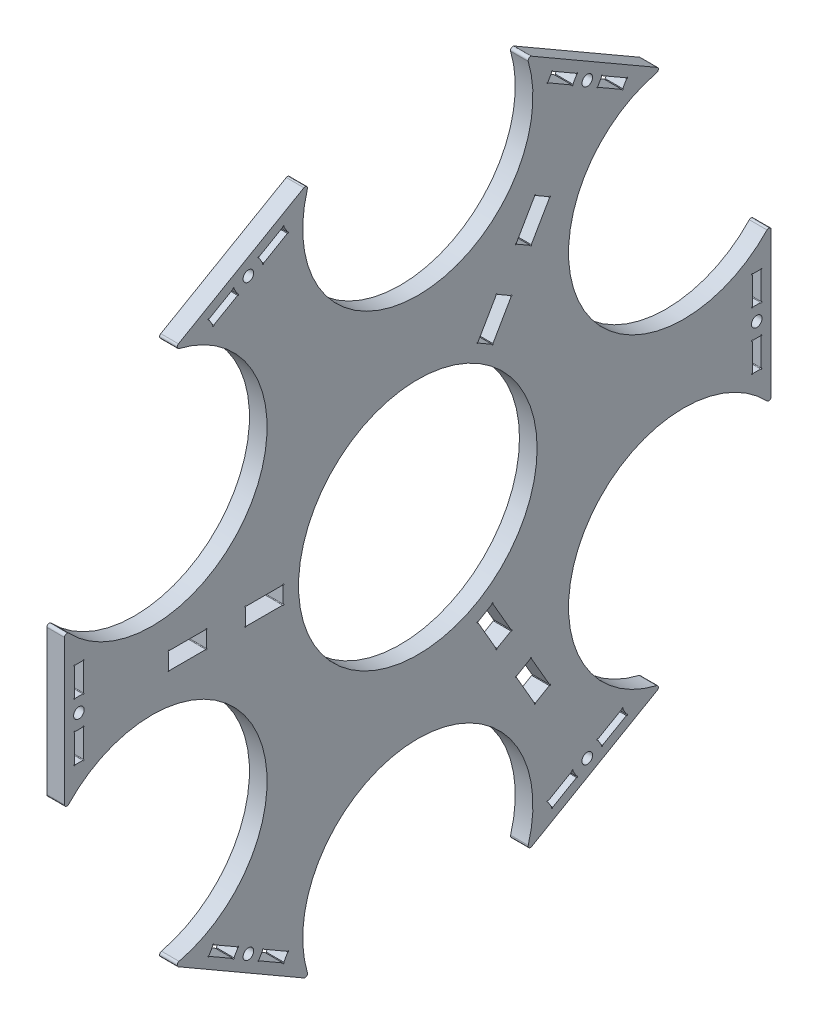
SolidWorks part; units mm, degrees
ref_plane "Front Plane" through (0, 0, 0) normal (0, 0, 1) x (1, 0, 0)
ref_plane "Top Plane" through (0, 0, 0) normal (0, 1, 0) x (1, 0, 0)
ref_plane "Right Plane" through (0, 0, 0) normal (1, 0, 0) x (0, 0, -1)
sketch "Sketch2" plane through (0, 0, 0) normal (1, 0, 0) x (0, 0, -1)
  line L0 (35.921, 114.3) -> (-35.921, 114.3) construction
  line L1 (81.0262, 88.2585) -> (35.921, 114.3)
  line L2 (116.9472, -26.0415) -> (116.9472, 26.0415)
  line L3 (35.921, -114.3) -> (81.0262, -88.2585)
  line L4 (-81.0262, -88.2585) -> (-35.921, -114.3)
  line L5 (-116.9472, 26.0415) -> (-116.9472, -26.0415)
  line L6 (-35.921, 114.3) -> (-81.0262, 88.2585)
  circle A0 centre (0, 0) radius 101.6 construction
  arc A1 (-35.921, 114.3) -> (35.921, 114.3) centre (0, 101.6) ccw
  arc A2 (81.0262, 88.2585) -> (116.9472, 26.0415) centre (87.9882, 50.8) ccw
  arc A3 (116.9472, -26.0415) -> (81.0262, -88.2585) centre (87.9882, -50.8) ccw
  arc A4 (35.921, -114.3) -> (-35.921, -114.3) centre (0, -101.6) ccw
  arc A5 (-81.0262, -88.2585) -> (-116.9472, -26.0415) centre (-87.9882, -50.8) ccw
  arc A6 (-116.9472, 26.0415) -> (-81.0262, 88.2585) centre (-87.9882, 50.8) ccw
  circle A7 centre (0, 0) radius 39.4875
  point P23 (0, 0)
  point P34 (0, 0)
  dimension "D1" = 203.2
  dimension "D2" = 114.3
  dimension "D3" = 76.2
  dimension "D6" = 78.9749
  dimension "D4" = 6
  dimension "D5" = 6
extrude "Boss-Extrude1" add sketch "Sketch2" along normal blind 5.842 contours A6 L5 A5 L4 A4 L3 A3 L2 A2 L1 A1 L6 region at (0, 30.1147, -52.1602)
fillet "Fillet1" radius 0.7937 12 edges at (2.921, -114.3, 35.921) (2.921, -114.3, -35.921) (2.921, -88.2585, -81.0262) (2.921, -26.0415, -116.9472) (2.921, 88.2585, -81.0262) (2.921, 26.0415, -116.9472) (2.921, -88.2585, 81.0262) (2.921, -26.0415, 116.9472) (2.921, 26.0415, 116.9472) (2.921, 88.2585, 81.0262) (2.921, 114.3, -35.921) (2.921, 114.3, 35.921)
sketch "Sketch3" plane through (5.842, 0, 0) normal (1, 0, 0) x (0, 0, -1)
  line L0 (0, 0) -> (0, 50.8) construction
  line L2 (6.1516, 53.721) -> (-6.1516, 53.721)
  line L3 (6.35, 53.5226) -> (6.35, 48.0774)
  line L4 (6.1516, 47.879) -> (-6.1516, 47.879)
  line L5 (-6.35, 53.5226) -> (-6.35, 48.0774)
  line L6 (6.35, 53.721) -> (-6.35, 47.879) construction
  line L7 (6.35, 47.879) -> (-6.35, 53.721) construction
  arc A0 (-6.1516, 53.721) -> (-6.35, 53.5226) centre (-6.35, 53.721) ccw
  arc A1 (-6.35, 48.0774) -> (-6.1516, 47.879) centre (-6.35, 47.879) ccw
  arc A2 (6.1516, 47.879) -> (6.35, 48.0774) centre (6.35, 47.879) ccw
  arc A3 (6.35, 53.5226) -> (6.1516, 53.721) centre (6.35, 53.721) ccw
  dimension "D4" = 0.3969
  dimension "D5" = 0.3969
  dimension "D6" = 0.3969
  dimension "D7" = 0.3969
  dimension "D1" = 50.8
  dimension "D2" = 12.7
  dimension "D3" = 5.842
extrude "Cut-Extrude2" [suppressed] cut sketch "Sketch3" against normal through all
pattern_circular "CirPattern1" [suppressed] count 3 every 120 of bodies 112
sketch "Sketch4" plane through (5.842, 0, 0) normal (1, 0, 0) x (0, 0, -1)
  line L0 (0, 0) -> (25.4, 43.9941) construction
  line L1 (26.0386, 50.8422) -> (19.7886, 40.0169)
  line L2 (26.0386, 50.8422) -> (31.0114, 47.9712)
  line L3 (19.7886, 40.0169) -> (24.7614, 37.1459)
  line L4 (31.0114, 47.9712) -> (24.7614, 37.1459)
  line L5 (26.0386, 50.8422) -> (24.7614, 37.1459) construction
  line L6 (19.7886, 40.0169) -> (31.0114, 47.9712) construction
  line L7 (0, 0) -> (0, 63.5) construction
  line L8 (31.0114, -47.9712) -> (24.7614, -37.1459)
  line L9 (31.0114, -47.9712) -> (26.0386, -50.8422)
  line L10 (24.7614, -37.1459) -> (19.7886, -40.0169)
  line L11 (26.0386, -50.8422) -> (19.7886, -40.0169)
  line L12 (31.0114, -47.9712) -> (19.7886, -40.0169) construction
  line L13 (24.7614, -37.1459) -> (26.0386, -50.8422) construction
  line L14 (-57.05, -2.871) -> (-44.55, -2.871)
  line L15 (-57.05, -2.871) -> (-57.05, 2.871)
  line L16 (-44.55, -2.871) -> (-44.55, 2.871)
  line L17 (-57.05, 2.871) -> (-44.55, 2.871)
  line L18 (-57.05, -2.871) -> (-44.55, 2.871) construction
  line L19 (-44.55, -2.871) -> (-57.05, 2.871) construction
  arc A0 (-36.5501, 112.3566) -> (36.5501, 112.3566) centre (0, 101.6) ccw construction
  point P21 (0, 0)
  dimension "D1" = 50.8
  dimension "D2" = 12.5
  dimension "D3" = 5.742
  dimension "D4" = 30
extrude "Cut-Extrude3" cut sketch "Sketch4" against normal through all
sketch "Sketch5" plane through (5.842, 0, 0) normal (1, 0, 0) x (0, 0, -1)
  line L0 (22.9136, 45.4296) -> (27.8864, 42.5586) construction
  line L3 (26.0386, 50.8422) -> (19.7886, 40.0169) construction
  line L4 (24.7614, 37.1459) -> (31.0114, 47.9712) construction
  line L7 (27.8864, -42.5586) -> (22.9136, -45.4296) construction
  line L8 (-50.8, -2.871) -> (-50.8, 2.871) construction
  circle A0 centre (26.0386, 50.8422) radius 0.1984
  circle A1 centre (31.0114, 47.9712) radius 0.1984
  circle A2 centre (24.7614, 37.1459) radius 0.1984
  circle A3 centre (19.7886, 40.0169) radius 0.1984
  circle A4 centre (31.0114, -47.9712) radius 0.1984
  circle A5 centre (26.0386, -50.8422) radius 0.1984
  circle A6 centre (19.7886, -40.0169) radius 0.1984
  circle A7 centre (24.7614, -37.1459) radius 0.1984
  circle A8 centre (-57.05, -2.871) radius 0.1984
  circle A9 centre (-57.05, 2.871) radius 0.1984
  circle A10 centre (-44.55, 2.871) radius 0.1984
  circle A11 centre (-44.55, -2.871) radius 0.1984
  point P38 (0, 0)
  dimension "D1" = 0.3969
  dimension "D2" = 0.3969
extrude "Cut-Extrude4" cut sketch "Sketch5" against normal through all
sketch "Sketch6" plane through (5.842, 0, 0) normal (1, 0, 0) x (0, 0, -1)
  line L0 (-58.4736, 101.2793) -> (0, 0) construction
  line L1 (-37.7084, 113.2681) -> (-79.2388, 89.2905) construction
  line L2 (-32.1468, 110.9798) -> (-80.0379, 83.3298) construction
  line L3 (-67.7219, 88.7229) -> (-60.9606, 96.0618) construction
  line L4 (-59.4731, 93.4854) -> (-69.2094, 91.2993) construction
  line L5 (-67.5501, 88.8221) -> (-59.6449, 93.3861)
  line L6 (-67.8212, 88.8947) -> (-69.1102, 91.1274)
  line L7 (-59.5723, 93.6572) -> (-60.8613, 95.8899)
  line L8 (-69.0376, 91.3985) -> (-61.1324, 95.9626)
  line L9 (-51.2242, 98.2479) -> (-44.4628, 105.5868) construction
  line L10 (-42.9753, 103.0104) -> (-52.7117, 100.8243) construction
  line L11 (-44.6346, 105.4876) -> (-52.5398, 100.9235)
  line L12 (-51.3234, 98.4197) -> (-52.6124, 100.6524)
  line L13 (-43.0745, 103.1822) -> (-44.3636, 105.4149)
  line L14 (-43.1471, 102.9111) -> (-51.0523, 98.3471)
  line L15 (43.1471, 102.9111) -> (51.0523, 98.3471)
  line L16 (43.0745, 103.1822) -> (44.3636, 105.4149)
  line L17 (51.3234, 98.4197) -> (52.6124, 100.6524)
  line L18 (44.6346, 105.4876) -> (52.5398, 100.9235)
  line L19 (69.0376, 91.3985) -> (61.1324, 95.9626)
  line L20 (59.5723, 93.6572) -> (60.8613, 95.8899)
  line L21 (67.8212, 88.8947) -> (69.1102, 91.1274)
  line L22 (67.5501, 88.8221) -> (59.6449, 93.3861)
  line L23 (58.4736, 101.2793) -> (0, 0) construction
  line L24 (80.0379, 83.3298) -> (32.1468, 110.9798) construction
  line L25 (42.9753, 103.0104) -> (52.7117, 100.8243) construction
  line L26 (51.2242, 98.2479) -> (44.4628, 105.5868) construction
  line L27 (59.4731, 93.4854) -> (69.2094, 91.2993) construction
  line L28 (67.7219, 88.7229) -> (60.9606, 96.0618) construction
  line L29 (110.6972, 14.0891) -> (110.6972, 4.9609)
  line L30 (110.8957, 14.2875) -> (113.4738, 14.2875)
  line L31 (110.8957, 4.7625) -> (113.4738, 4.7625)
  line L32 (113.6722, 14.0891) -> (113.6722, 4.9609)
  line L33 (113.6722, -14.0891) -> (113.6722, -4.9609)
  line L34 (110.8957, -4.7625) -> (113.4738, -4.7625)
  line L35 (110.8957, -14.2875) -> (113.4738, -14.2875)
  line L36 (110.6972, -14.0891) -> (110.6972, -4.9609)
  line L37 (116.9472, 0) -> (0, 0) construction
  line L38 (112.1847, -27.65) -> (112.1847, 27.65) construction
  line L39 (110.6972, 14.2875) -> (113.6722, 4.7625) construction
  line L40 (110.6972, 4.7625) -> (113.6722, 14.2875) construction
  line L41 (110.6972, -4.7625) -> (113.6722, -14.2875) construction
  line L42 (110.6972, -14.2875) -> (113.6722, -4.7625) construction
  line L43 (67.5501, -88.8221) -> (59.6449, -93.3861)
  line L44 (67.8212, -88.8947) -> (69.1102, -91.1274)
  line L45 (59.5723, -93.6572) -> (60.8613, -95.8899)
  line L46 (69.0376, -91.3985) -> (61.1324, -95.9626)
  line L47 (44.6346, -105.4876) -> (52.5398, -100.9235)
  line L48 (51.3234, -98.4197) -> (52.6124, -100.6524)
  line L49 (43.0745, -103.1822) -> (44.3636, -105.4149)
  line L50 (43.1471, -102.9111) -> (51.0523, -98.3471)
  line L51 (58.4736, -101.2793) -> (0, 0) construction
  line L52 (32.1468, -110.9798) -> (80.0379, -83.3298) construction
  line L53 (67.7219, -88.7229) -> (60.9606, -96.0618) construction
  line L54 (59.4731, -93.4854) -> (69.2094, -91.2993) construction
  line L55 (51.2242, -98.2479) -> (44.4628, -105.5868) construction
  line L56 (42.9753, -103.0104) -> (52.7117, -100.8243) construction
  line L57 (-43.1471, -102.9111) -> (-51.0523, -98.3471)
  line L58 (-43.0745, -103.1822) -> (-44.3636, -105.4149)
  line L59 (-51.3234, -98.4197) -> (-52.6124, -100.6524)
  line L60 (-44.6346, -105.4876) -> (-52.5398, -100.9235)
  line L61 (-69.0376, -91.3985) -> (-61.1324, -95.9626)
  line L62 (-59.5723, -93.6572) -> (-60.8613, -95.8899)
  line L63 (-67.8212, -88.8947) -> (-69.1102, -91.1274)
  line L64 (-67.5501, -88.8221) -> (-59.6449, -93.3861)
  line L65 (-58.4736, -101.2793) -> (0, 0) construction
  line L66 (-80.0379, -83.3298) -> (-32.1468, -110.9798) construction
  line L67 (-42.9753, -103.0104) -> (-52.7117, -100.8243) construction
  line L68 (-51.2242, -98.2479) -> (-44.4628, -105.5868) construction
  line L69 (-59.4731, -93.4854) -> (-69.2094, -91.2993) construction
  line L70 (-67.7219, -88.7229) -> (-60.9606, -96.0618) construction
  line L71 (-110.6972, -14.0891) -> (-110.6972, -4.9609)
  line L72 (-110.8957, -14.2875) -> (-113.4738, -14.2875)
  line L73 (-110.8957, -4.7625) -> (-113.4738, -4.7625)
  line L74 (-113.6722, -14.0891) -> (-113.6722, -4.9609)
  line L75 (-113.6722, 14.0891) -> (-113.6722, 4.9609)
  line L76 (-110.8957, 4.7625) -> (-113.4738, 4.7625)
  line L77 (-110.8957, 14.2875) -> (-113.4738, 14.2875)
  line L78 (-110.6972, 14.0891) -> (-110.6972, 4.9609)
  line L79 (-116.9472, 0) -> (0, 0) construction
  line L80 (-112.1847, 27.65) -> (-112.1847, -27.65) construction
  line L81 (-110.6972, -14.2875) -> (-113.6722, -4.7625) construction
  line L82 (-110.6972, -4.7625) -> (-113.6722, -14.2875) construction
  line L83 (-110.6972, 4.7625) -> (-113.6722, 14.2875) construction
  line L84 (-110.6972, 14.2875) -> (-113.6722, 4.7625) construction
  arc A0 (-44.3636, 105.4149) -> (-44.6346, 105.4876) centre (-44.4628, 105.5868) ccw
  arc A1 (-43.1471, 102.9111) -> (-43.0745, 103.1822) centre (-42.9753, 103.0104) ccw
  arc A2 (-51.3234, 98.4197) -> (-51.0523, 98.3471) centre (-51.2242, 98.2479) ccw
  arc A3 (-52.5398, 100.9235) -> (-52.6124, 100.6524) centre (-52.7117, 100.8243) ccw
  arc A4 (-61.1324, 95.9626) -> (-60.8613, 95.8899) centre (-60.9606, 96.0618) cw
  arc A5 (-59.5723, 93.6572) -> (-59.6449, 93.3861) centre (-59.4731, 93.4854) cw
  arc A6 (-67.5501, 88.8221) -> (-67.8212, 88.8947) centre (-67.7219, 88.7229) cw
  arc A7 (-69.1102, 91.1274) -> (-69.0376, 91.3985) centre (-69.2094, 91.2993) cw
  arc A8 (69.1102, 91.1274) -> (69.0376, 91.3985) centre (69.2094, 91.2993) ccw
  arc A9 (67.5501, 88.8221) -> (67.8212, 88.8947) centre (67.7219, 88.7229) ccw
  arc A10 (59.5723, 93.6572) -> (59.6449, 93.3861) centre (59.4731, 93.4854) ccw
  arc A11 (61.1324, 95.9626) -> (60.8613, 95.8899) centre (60.9606, 96.0618) ccw
  arc A12 (52.5398, 100.9235) -> (52.6124, 100.6524) centre (52.7117, 100.8243) cw
  arc A13 (51.3234, 98.4197) -> (51.0523, 98.3471) centre (51.2242, 98.2479) cw
  arc A14 (43.1471, 102.9111) -> (43.0745, 103.1822) centre (42.9753, 103.0104) cw
  arc A15 (44.3636, 105.4149) -> (44.6346, 105.4876) centre (44.4628, 105.5868) cw
  arc A16 (113.4738, -14.2875) -> (113.6722, -14.0891) centre (113.6722, -14.2875) ccw
  arc A17 (110.6972, -14.0891) -> (110.8957, -14.2875) centre (110.6972, -14.2875) ccw
  arc A18 (110.8957, -4.7625) -> (110.6972, -4.9609) centre (110.6972, -4.7625) ccw
  arc A19 (113.6722, -4.9609) -> (113.4738, -4.7625) centre (113.6722, -4.7625) ccw
  arc A20 (113.6722, 4.9609) -> (113.4738, 4.7625) centre (113.6722, 4.7625) cw
  arc A21 (110.8957, 4.7625) -> (110.6972, 4.9609) centre (110.6972, 4.7625) cw
  arc A22 (110.6972, 14.0891) -> (110.8957, 14.2875) centre (110.6972, 14.2875) cw
  arc A23 (113.4738, 14.2875) -> (113.6722, 14.0891) centre (113.6722, 14.2875) cw
  arc A24 (44.3636, -105.4149) -> (44.6346, -105.4876) centre (44.4628, -105.5868) ccw
  arc A25 (43.1471, -102.9111) -> (43.0745, -103.1822) centre (42.9753, -103.0104) ccw
  arc A26 (51.3234, -98.4197) -> (51.0523, -98.3471) centre (51.2242, -98.2479) ccw
  arc A27 (52.5398, -100.9235) -> (52.6124, -100.6524) centre (52.7117, -100.8243) ccw
  arc A28 (61.1324, -95.9626) -> (60.8613, -95.8899) centre (60.9606, -96.0618) cw
  arc A29 (59.5723, -93.6572) -> (59.6449, -93.3861) centre (59.4731, -93.4854) cw
  arc A30 (67.5501, -88.8221) -> (67.8212, -88.8947) centre (67.7219, -88.7229) cw
  arc A31 (69.1102, -91.1274) -> (69.0376, -91.3985) centre (69.2094, -91.2993) cw
  arc A32 (-69.1102, -91.1274) -> (-69.0376, -91.3985) centre (-69.2094, -91.2993) ccw
  arc A33 (-67.5501, -88.8221) -> (-67.8212, -88.8947) centre (-67.7219, -88.7229) ccw
  arc A34 (-59.5723, -93.6572) -> (-59.6449, -93.3861) centre (-59.4731, -93.4854) ccw
  arc A35 (-61.1324, -95.9626) -> (-60.8613, -95.8899) centre (-60.9606, -96.0618) ccw
  arc A36 (-52.5398, -100.9235) -> (-52.6124, -100.6524) centre (-52.7117, -100.8243) cw
  arc A37 (-51.3234, -98.4197) -> (-51.0523, -98.3471) centre (-51.2242, -98.2479) cw
  arc A38 (-43.1471, -102.9111) -> (-43.0745, -103.1822) centre (-42.9753, -103.0104) cw
  arc A39 (-44.3636, -105.4149) -> (-44.6346, -105.4876) centre (-44.4628, -105.5868) cw
  arc A40 (-113.4738, 14.2875) -> (-113.6722, 14.0891) centre (-113.6722, 14.2875) ccw
  arc A41 (-110.6972, 14.0891) -> (-110.8957, 14.2875) centre (-110.6972, 14.2875) ccw
  arc A42 (-110.8957, 4.7625) -> (-110.6972, 4.9609) centre (-110.6972, 4.7625) ccw
  arc A43 (-113.6722, 4.9609) -> (-113.4738, 4.7625) centre (-113.6722, 4.7625) ccw
  arc A44 (-113.6722, -4.9609) -> (-113.4738, -4.7625) centre (-113.6722, -4.7625) cw
  arc A45 (-110.8957, -4.7625) -> (-110.6972, -4.9609) centre (-110.6972, -4.7625) cw
  arc A46 (-110.6972, -14.0891) -> (-110.8957, -14.2875) centre (-110.6972, -14.2875) cw
  arc A47 (-113.4738, -14.2875) -> (-113.6722, -14.0891) centre (-113.6722, -14.2875) cw
  circle A48 centre (-56.0924, 97.1548) radius 1.7526
  circle A49 centre (56.0924, 97.1548) radius 1.7526
  circle A50 centre (112.1847, 0) radius 1.7526
  circle A51 centre (56.0924, -97.1548) radius 1.7526
  circle A52 centre (-56.0924, -97.1548) radius 1.7526
  circle A53 centre (-112.1847, 0) radius 1.7526
  point P8 (-56.0924, 97.1548)
  point P9 (-56.0924, 97.1548)
  point P18 (-47.8435, 101.9173)
  point P34 (-64.3412, 92.3923)
  point P41 (56.0924, 97.1548)
  point P42 (56.0924, 97.1548)
  point P51 (64.3412, 92.3923)
  point P67 (47.8435, 101.9173)
  point P72 (112.1847, 0)
  point P73 (112.1847, 0)
  point P82 (112.1847, -9.525)
  point P98 (112.1847, 9.525)
  point P103 (56.0924, -97.1548)
  point P104 (56.0924, -97.1548)
  point P113 (47.8435, -101.9173)
  point P129 (64.3412, -92.3923)
  point P134 (-56.0924, -97.1548)
  point P135 (-56.0924, -97.1548)
  point P144 (-64.3412, -92.3923)
  point P160 (-47.8435, -101.9173)
  point P165 (-112.1847, 0)
  point P166 (-112.1847, 0)
  point P175 (-112.1847, 9.525)
  point P191 (-112.1847, -9.525)
  point P192 (0, 0)
  point P205 (0, 0)
  dimension "D5" = 0.3969
  dimension "D6" = 0.3969
  dimension "D7" = 0.3969
  dimension "D8" = 0.3969
  dimension "D4" = 3.5052
  dimension "D1" = 4.7625
  dimension "D2" = 9.525
  dimension "D3" = 6
  dimension "D9" = 6
extrude "Cut-Extrude5" cut sketch "Sketch6" against normal through all
sketch "Sketch7" plane through (5.842, 0, 0) normal (1, 0, 0) x (0, 0, -1)
  line L0 (34.975, 60.5785) -> (58.4736, 101.2793) construction
  line L2 (79.2388, 89.2905) -> (37.7084, 113.2681) construction
  line L6 (38.9105, -72.7401) -> (43.5395, -70.0675)
  line L7 (43.6121, -69.7964) -> (37.5606, -59.3148)
  line L8 (37.2895, -59.2422) -> (32.6605, -61.9148)
  line L9 (32.5879, -62.1858) -> (38.6394, -72.6674)
  line L10 (43.5395, 70.0675) -> (38.9105, 72.7401)
  line L11 (38.6394, 72.6674) -> (32.5879, 62.1858)
  line L12 (32.6605, 61.9148) -> (37.2895, 59.2422)
  line L13 (37.5606, 59.3148) -> (43.6121, 69.7964)
  line L14 (34.975, -60.5785) -> (58.4736, -101.2793) construction
  line L15 (-82.45, 2.6726) -> (-82.45, -2.6726)
  line L16 (-82.2516, -2.871) -> (-70.1484, -2.871)
  line L17 (-69.95, -2.6726) -> (-69.95, 2.6726)
  line L18 (-70.1484, 2.871) -> (-82.2516, 2.871)
  line L19 (-69.95, 0) -> (-116.9472, 0) construction
  arc A4 (38.6394, -72.6674) -> (38.9105, -72.7401) centre (38.7386, -72.8393) ccw
  arc A5 (43.5395, -70.0675) -> (43.6121, -69.7964) centre (43.7114, -69.9683) ccw
  arc A6 (37.5606, -59.3148) -> (37.2895, -59.2422) centre (37.4614, -59.143) ccw
  arc A7 (32.6605, -61.9148) -> (32.5879, -62.1858) centre (32.4886, -62.014) ccw
  arc A8 (43.6121, 69.7964) -> (43.5395, 70.0675) centre (43.7114, 69.9683) ccw
  arc A9 (38.9105, 72.7401) -> (38.6394, 72.6674) centre (38.7386, 72.8393) ccw
  arc A10 (32.5879, 62.1858) -> (32.6605, 61.9148) centre (32.4886, 62.014) ccw
  arc A11 (37.2895, 59.2422) -> (37.5606, 59.3148) centre (37.4614, 59.143) ccw
  arc A12 (-82.2516, 2.871) -> (-82.45, 2.6726) centre (-82.45, 2.871) ccw
  arc A13 (-82.45, -2.6726) -> (-82.2516, -2.871) centre (-82.45, -2.871) ccw
  arc A14 (-70.1484, -2.871) -> (-69.95, -2.6726) centre (-69.95, -2.871) ccw
  arc A15 (-69.95, 2.6726) -> (-70.1484, 2.871) centre (-69.95, 2.871) ccw
  point P47 (0, 0)
  dimension "D1" = 3
extrude "Cut-Extrude6" cut sketch "Sketch7" against normal through all
